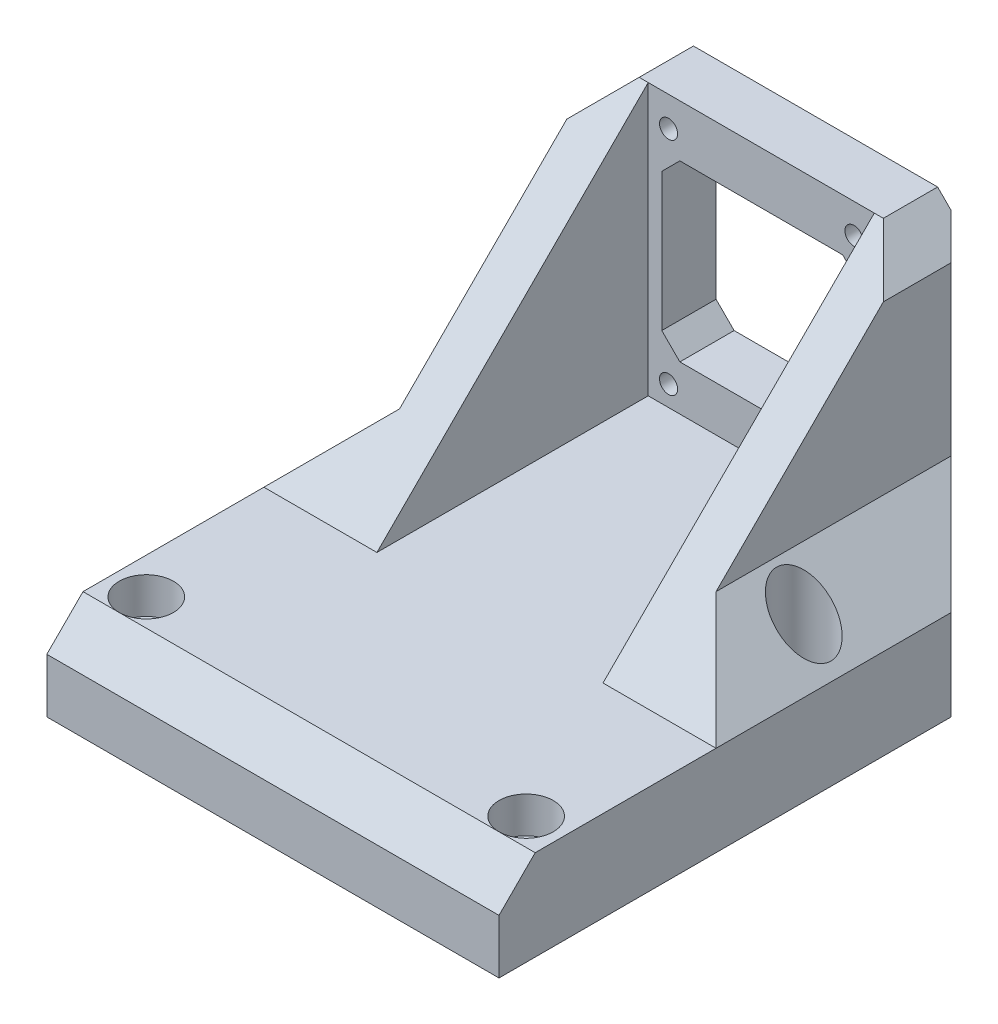
SolidWorks part; units mm, degrees
ref_plane "Front Plane" through (0, 0, 0) normal (0, 0, 1) x (1, 0, 0)
ref_plane "Top Plane" through (0, 0, 0) normal (0, 1, 0) x (1, 0, 0)
ref_plane "Right Plane" through (0, 0, 0) normal (1, 0, 0) x (0, 0, -1)
sketch "Sketch1" plane through (0, 0, 0) normal (0, 1, 0) x (1, 0, 0)
  line L1 (-25, 30) -> (25, 30)
  line L2 (-25, 30) -> (-25, -30)
  line L3 (-25, -30) -> (25, -30)
  line L4 (25, 30) -> (25, -30)
  line L5 (-25, 30) -> (25, -30) construction
  line L6 (-25, -30) -> (25, 30) construction
  point P0 (0, 0)
  dimension "D1" = 50
  dimension "D2" = 60
extrude "Boss-Extrude1" add sketch "Sketch1" along normal blind 10
sketch "Sketch2" plane through (0, 0, 0) normal (0, 1, 0) x (1, 0, 0)
  line L0 (-25, -30) -> (25, -30) construction
  line L1 (-21, -23) -> (21, -23) construction
  line L2 (-21, -23) -> (-21, 7.7) construction
  line L3 (-21, 7.7) -> (21, 7.7) construction
  line L4 (21, -23) -> (21, 7.7) construction
  line L5 (-21, -23) -> (21, 7.7) construction
  line L6 (-21, 7.7) -> (21, -23) construction
  circle A0 centre (-21, 7.7) radius 1.5
  circle A1 centre (-21, -23) radius 1.5
  circle A2 centre (21, 7.7) radius 1.5
  circle A3 centre (21, -23) radius 1.5
  point P0 (0, -7.65)
  dimension "D4" = 3
  dimension "D1" = 42
  dimension "D2" = 30.7
  dimension "D3" = 7
extrude "Cut-Extrude1" cut sketch "Sketch2" along normal blind 6
sketch "Sketch3" plane through (0, 6, 0) normal (0, -1, 0) x (1, 0, 0)
  circle A0 centre (-21, 23) radius 3
  circle A1 centre (21, 23) radius 3
  circle A2 centre (21, -7.7) radius 3
  circle A3 centre (-21, -7.7) radius 3
  dimension "D1" = 6
extrude "Cut-Extrude2" cut sketch "Sketch3" against normal up to next
sketch "Sketch5" plane through (0, 10, 0) normal (0, 1, 0) x (1, 0, 0)
  line L0 (25, 30) -> (-25, 30) construction
  line L1 (-12.5, 24) -> (12.5, 24)
  line L2 (-12.5, 24) -> (-12.5, 30)
  line L3 (-12.5, 30) -> (12.5, 30)
  line L4 (12.5, 24) -> (12.5, 30)
  line L5 (-12.5, 24) -> (12.5, 30) construction
  line L6 (-12.5, 30) -> (12.5, 24) construction
  point P0 (0, 27)
  dimension "D1" = 6
  dimension "D2" = 25
extrude "Boss-Extrude3" add sketch "Sketch5" along normal blind 30
sketch "Sketch6" plane through (0, 0, -30) normal (0, 0, -1) x (-1, 0, 0)
  line L0 (-25, 10) -> (-12.5, 10) construction
  line L1 (-11, 15) -> (11, 15)
  line L2 (-11, 15) -> (-11, 34.25)
  line L3 (-11, 34.25) -> (11, 34.25)
  line L4 (11, 15) -> (11, 34.25)
  line L5 (-11, 15) -> (11, 34.25) construction
  line L6 (-11, 34.25) -> (11, 15) construction
  point P0 (0, 24.625)
  dimension "D1" = 22
  dimension "D2" = 19.25
  dimension "D3" = 5
extrude "Cut-Extrude3" cut sketch "Sketch6" against normal up to next
sketch "Sketch7" plane through (0, 0, -24) normal (0, 0, 1) x (1, 0, 0)
  line L0 (-12.5, 10) -> (12.5, 10) construction
  line L1 (-10.25, 12.25) -> (10.25, 12.25) construction
  line L2 (-10.25, 12.25) -> (-10.25, 36.7) construction
  line L3 (-10.25, 36.7) -> (10.25, 36.7) construction
  line L4 (10.25, 12.25) -> (10.25, 36.7) construction
  line L5 (-10.25, 12.25) -> (10.25, 36.7) construction
  line L6 (-10.25, 36.7) -> (10.25, 12.25) construction
  circle A0 centre (10.25, 12.25) radius 1
  circle A1 centre (-10.25, 12.25) radius 1
  circle A2 centre (-10.25, 36.7) radius 1
  circle A3 centre (10.25, 36.7) radius 1
  point P0 (0, 24.475)
  dimension "D4" = 2
  dimension "D1" = 20.5
  dimension "D2" = 24.45
  dimension "D3" = 2.25
extrude "Cut-Extrude4" cut sketch "Sketch7" against normal blind 2.5
sketch "Sketch8" plane through (0, 0, -26.5) normal (0, 0, 1) x (1, 0, 0)
  circle A0 centre (-10.25, 36.7) radius 2
  circle A1 centre (10.25, 36.7) radius 2
  circle A2 centre (10.25, 12.25) radius 2
  circle A3 centre (-10.25, 12.25) radius 2
  dimension "D1" = 4
extrude "Cut-Extrude5" cut sketch "Sketch8" against normal up to next
sketch "Sketch9" plane through (12.5, 0, 0) normal (1, 0, 0) x (0, 0, -1)
  line L0 (30, 40) -> (24, 40)
  line L1 (24, 40) -> (-6, 10)
  line L3 (-30, 10) -> (30, 10) construction
  line L4 (-6, 10) -> (30, 10)
  line L5 (30, 10) -> (30, 40)
  line L6 (30, 40) -> (30, 10) construction
  dimension "D1" = 45
extrude "Boss-Extrude4" add sketch "Sketch9" along normal blind 5
mirror "Mirror1" about plane through (0, 0, 0) normal (1, 0, 0) of "Boss-Extrude4"
chamfer "Chamfer1" distance 7.5 angle 45 2 edges at (17.5, 10, -12) (-17.5, 10, -12)
chamfer "Chamfer2" distance 10 angle 45 2 edges at (-25, 5, -30) (25, 5, -30)
chamfer "Chamfer4" distance 6.5 angle 45 1 edges at (0, 0, -30)
chamfer "Chamfer5" distance 4 angle 45 2 edges at (17.5, 40, -25.75) (-17.5, 40, -25.75)
chamfer "Chamfer6" distance 4 angle 45 1 edges at (0, 10, 30)
chamfer "Chamfer7" distance 2 angle 45 4 edges at (-11, 34.25, -27) (-11, 15, -27) (11, 15, -27) (11, 34.25, -27)
